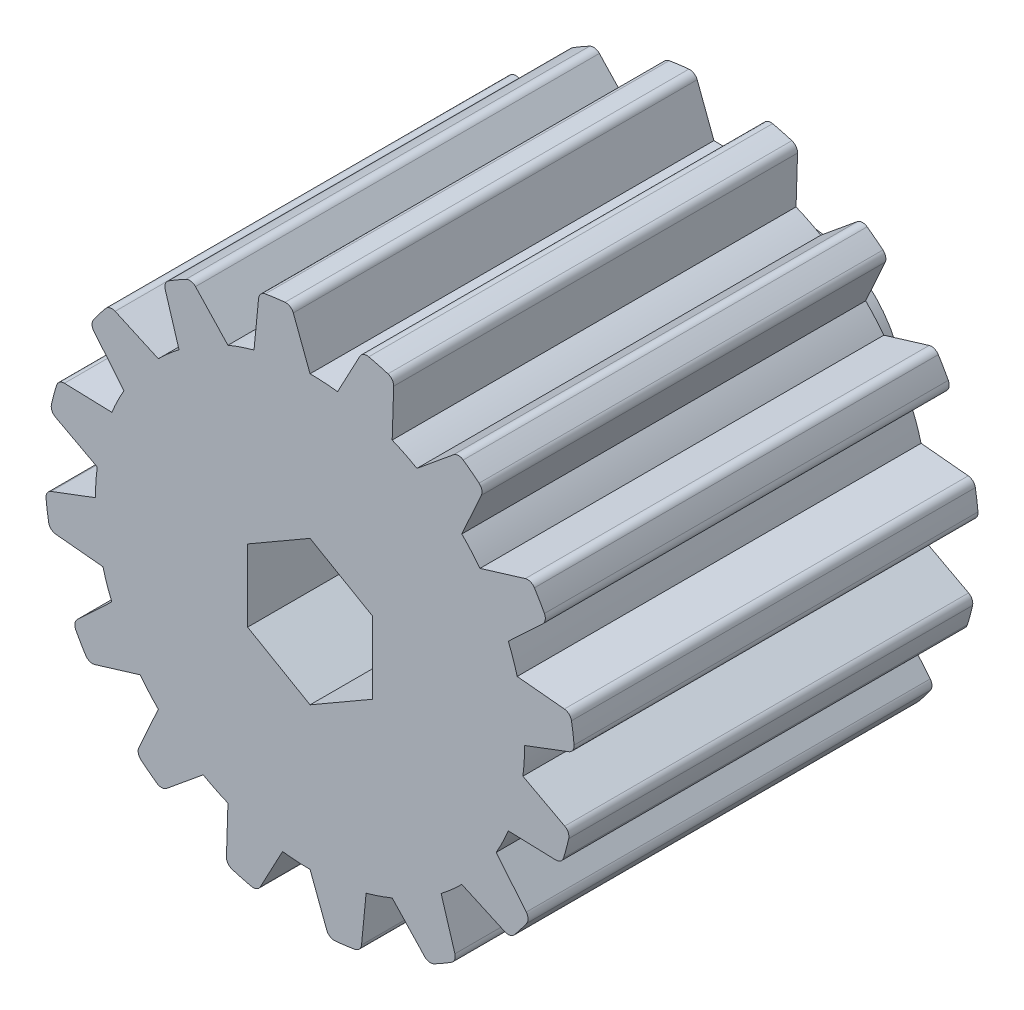
SolidWorks part; units mm, degrees
ref_plane "Alzado" through (0, 0, 0) normal (0, 0, 1) x (1, 0, 0)
ref_plane "Planta" through (0, 0, 0) normal (0, 1, 0) x (1, 0, 0)
ref_plane "Vista lateral" through (0, 0, 0) normal (1, 0, 0) x (0, 0, -1)
sketch "Croquis2" plane through (0, 0, 0) normal (0, 0, 1) x (1, 0, 0)
  line L0 (0, 0) -> (0, 7.9702) construction
  line L2 (-2.0817, 7.6936) -> (-1.9112, 9.4453)
  line L3 (-1.0408, 7.8319) -> (0, 0) construction
  line L4 (0, 7.9702) -> (-0.6221, 9.6166)
  line L5 (1.021, 7.9046) -> (1.8489, 9.4577)
  line L6 (3.0501, 7.3635) -> (3.1053, 9.1227)
  line L7 (3.9682, 6.9122) -> (5.3274, 8.0302)
  line L8 (5.6358, 5.6358) -> (6.3601, 7.2399)
  line L9 (6.3113, 4.8674) -> (7.9949, 5.3803)
  line L10 (7.3635, 3.0501) -> (8.6465, 4.2549)
  line L11 (7.6936, 2.0817) -> (9.4453, 1.9112)
  line L12 (7.9702, 0) -> (9.6166, 0.6221)
  line L13 (7.9046, -1.021) -> (9.4577, -1.8489)
  line L14 (7.3635, -3.0501) -> (9.1227, -3.1053)
  line L15 (6.9122, -3.9682) -> (8.0302, -5.3274)
  line L16 (5.6358, -5.6358) -> (7.2399, -6.3601)
  line L17 (4.8674, -6.3113) -> (5.3803, -7.9949)
  line L18 (3.0501, -7.3635) -> (4.2549, -8.6465)
  line L19 (2.0817, -7.6936) -> (1.9112, -9.4453)
  line L20 (0, -7.9702) -> (0.6221, -9.6166)
  line L21 (-1.021, -7.9046) -> (-1.8489, -9.4577)
  line L22 (-3.0501, -7.3635) -> (-3.1053, -9.1227)
  line L23 (-3.9682, -6.9122) -> (-5.3274, -8.0302)
  line L24 (-5.6358, -5.6358) -> (-6.3601, -7.2399)
  line L25 (-6.3113, -4.8674) -> (-7.9949, -5.3803)
  line L26 (-7.3635, -3.0501) -> (-8.6465, -4.2549)
  line L27 (-7.6936, -2.0817) -> (-9.4453, -1.9112)
  line L28 (-7.9702, 0) -> (-9.6166, -0.6221)
  line L29 (-7.9046, 1.021) -> (-9.4577, 1.8489)
  line L30 (-7.3635, 3.0501) -> (-9.1227, 3.1053)
  line L31 (-6.9122, 3.9682) -> (-8.0302, 5.3274)
  line L32 (-5.6358, 5.6358) -> (-7.2399, 6.3601)
  line L33 (-4.8674, 6.3113) -> (-5.3803, 7.9949)
  line L34 (-3.0501, 7.3635) -> (-4.2549, 8.6465)
  arc A0 (-4.8674, 6.3113) -> (-5.6358, 5.6358) centre (0, 0) ccw
  arc A1 (-7.5914, 6.2764) -> (-8.0413, 5.6886) centre (0, 0) ccw
  arc A2 (-1.6636, 9.7085) -> (-1.9112, 9.4453) centre (-1.6129, 9.4128) ccw
  arc A3 (-0.9298, 9.806) -> (-0.6221, 9.6166) centre (-0.9015, 9.5074) cw
  arc A4 (2.1783, 9.6061) -> (1.8489, 9.4577) centre (2.112, 9.3135) ccw
  arc A5 (2.8935, 9.4154) -> (3.1053, 9.1227) centre (2.8054, 9.1286) cw
  arc A6 (5.6886, 8.0413) -> (5.3274, 8.0302) centre (5.5153, 7.7964) ccw
  arc A7 (6.2764, 7.5914) -> (6.3601, 7.2399) centre (6.0852, 7.3602) cw
  arc A8 (8.3328, 5.2523) -> (7.9949, 5.3803) centre (8.0791, 5.0923) ccw
  arc A9 (8.7037, 4.6117) -> (8.6465, 4.2549) centre (8.4387, 4.4712) cw
  arc A10 (9.7085, 1.6636) -> (9.4453, 1.9112) centre (9.4128, 1.6129) ccw
  arc A11 (9.806, 0.9298) -> (9.6166, 0.6221) centre (9.5074, 0.9015) cw
  arc A12 (9.6061, -2.1783) -> (9.4577, -1.8489) centre (9.3135, -2.112) ccw
  arc A13 (9.4154, -2.8935) -> (9.1227, -3.1053) centre (9.1286, -2.8054) cw
  arc A14 (8.0413, -5.6886) -> (8.0302, -5.3274) centre (7.7964, -5.5153) ccw
  arc A15 (7.5914, -6.2764) -> (7.2399, -6.3601) centre (7.3602, -6.0852) cw
  arc A16 (5.2523, -8.3328) -> (5.3803, -7.9949) centre (5.0923, -8.0791) ccw
  arc A17 (4.6117, -8.7037) -> (4.2549, -8.6465) centre (4.4712, -8.4387) cw
  arc A18 (1.6636, -9.7085) -> (1.9112, -9.4453) centre (1.6129, -9.4128) ccw
  arc A19 (0.9298, -9.806) -> (0.6221, -9.6166) centre (0.9015, -9.5074) cw
  arc A20 (-2.1783, -9.6061) -> (-1.8489, -9.4577) centre (-2.112, -9.3135) ccw
  arc A21 (-2.8935, -9.4154) -> (-3.1053, -9.1227) centre (-2.8054, -9.1286) cw
  arc A22 (-5.6886, -8.0413) -> (-5.3274, -8.0302) centre (-5.5153, -7.7964) ccw
  arc A23 (-6.2764, -7.5914) -> (-6.3601, -7.2399) centre (-6.0852, -7.3602) cw
  arc A24 (-8.3328, -5.2523) -> (-7.9949, -5.3803) centre (-8.0791, -5.0923) ccw
  arc A25 (-8.7037, -4.6117) -> (-8.6465, -4.2549) centre (-8.4387, -4.4712) cw
  arc A26 (-9.7085, -1.6636) -> (-9.4453, -1.9112) centre (-9.4128, -1.6129) ccw
  arc A27 (-9.806, -0.9298) -> (-9.6166, -0.6221) centre (-9.5074, -0.9015) cw
  arc A28 (-9.6061, 2.1783) -> (-9.4577, 1.8489) centre (-9.3135, 2.112) ccw
  arc A29 (-9.4154, 2.8935) -> (-9.1227, 3.1053) centre (-9.1286, 2.8054) cw
  arc A30 (-8.0413, 5.6886) -> (-8.0302, 5.3274) centre (-7.7964, 5.5153) ccw
  arc A31 (-7.5914, 6.2764) -> (-7.2399, 6.3601) centre (-7.3602, 6.0852) cw
  arc A32 (-5.2523, 8.3328) -> (-5.3803, 7.9949) centre (-5.0923, 8.0791) ccw
  arc A33 (-4.6117, 8.7037) -> (-4.2549, 8.6465) centre (-4.4712, 8.4387) cw
  arc A34 (-4.6117, 8.7037) -> (-5.2523, 8.3328) centre (0, 0) ccw
  arc A35 (-0.9298, 9.806) -> (-1.6636, 9.7085) centre (0, 0) ccw
  arc A36 (2.8935, 9.4154) -> (2.1783, 9.6061) centre (0, 0) ccw
  arc A37 (6.2764, 7.5914) -> (5.6886, 8.0413) centre (0, 0) ccw
  arc A38 (8.7037, 4.6117) -> (8.3328, 5.2523) centre (0, 0) ccw
  arc A39 (9.4154, -2.8935) -> (9.6061, -2.1783) centre (0, 0) ccw
  arc A40 (7.5914, -6.2764) -> (8.0413, -5.6886) centre (0, 0) ccw
  arc A41 (-9.4154, 2.8935) -> (-9.6061, 2.1783) centre (0, 0) ccw
  arc A42 (-9.806, -0.9298) -> (-9.7085, -1.6636) centre (0, 0) ccw
  arc A43 (-8.7037, -4.6117) -> (-8.3328, -5.2523) centre (0, 0) ccw
  arc A44 (-6.2764, -7.5914) -> (-5.6886, -8.0413) centre (0, 0) ccw
  arc A45 (-2.8935, -9.4154) -> (-2.1783, -9.6061) centre (0, 0) ccw
  arc A46 (0.9298, -9.806) -> (1.6636, -9.7085) centre (0, 0) ccw
  arc A47 (4.6117, -8.7037) -> (5.2523, -8.3328) centre (0, 0) ccw
  arc A48 (-2.0817, 7.6936) -> (-3.0501, 7.3635) centre (0, 0) ccw
  arc A49 (1.021, 7.9046) -> (0, 7.9702) centre (0, 0) ccw
  arc A50 (3.9682, 6.9122) -> (3.0501, 7.3635) centre (0, 0) ccw
  arc A51 (6.3113, 4.8674) -> (5.6358, 5.6358) centre (0, 0) ccw
  arc A52 (7.6936, 2.0817) -> (7.3635, 3.0501) centre (0, 0) ccw
  arc A53 (7.9046, -1.021) -> (7.9702, 0) centre (0, 0) ccw
  arc A54 (9.806, 0.9298) -> (9.7085, 1.6636) centre (0, 0) ccw
  arc A55 (6.9122, -3.9682) -> (7.3635, -3.0501) centre (0, 0) ccw
  arc A56 (4.8674, -6.3113) -> (5.6358, -5.6358) centre (0, 0) ccw
  arc A57 (2.0817, -7.6936) -> (3.0501, -7.3635) centre (0, 0) ccw
  arc A58 (-1.021, -7.9046) -> (0, -7.9702) centre (0, 0) ccw
  arc A59 (-3.9682, -6.9122) -> (-3.0501, -7.3635) centre (0, 0) ccw
  arc A60 (-6.3113, -4.8674) -> (-5.6358, -5.6358) centre (0, 0) ccw
  arc A61 (-7.6936, -2.0817) -> (-7.3635, -3.0501) centre (0, 0) ccw
  arc A62 (-7.9046, 1.021) -> (-7.9702, 0) centre (0, 0) ccw
  arc A63 (-6.9122, 3.9682) -> (-7.3635, 3.0501) centre (0, 0) ccw
  dimension "D1" = 2.1
  dimension "D2" = 19.7
  dimension "D3" = 15.9404
  dimension "D6" = 0.6
  dimension "D4" = 1.76
extrude "Saliente-Extruir1" add sketch "Croquis2" along normal blind 15
sketch "Croquis5" plane through (0, 0, 0) normal (0, 0, -1) x (-1, 0, 0)
  circle A0 centre (0, 0) radius 4.5
  dimension "D1" = 9
extrude "Saliente-Extruir2" add sketch "Croquis5" along normal blind 6
scale "Escala1" scale about origin uniform scaling yes scale factor 1.5
sketch "Croquis7" plane through (0, 0, -9) normal (0, 0, -1) x (-1, 0, 0)
  circle A0 centre (0, 0) radius 10
  dimension "D1" = 20
extrude "Cortar-Extruir3" cut sketch "Croquis7" against normal blind 5.8 and the other way through all
sketch "Croquis8" plane through (0, 0, -3.2) normal (0, 0, -1) x (-1, 0, 0)
  circle A3 centre (0, 0) radius 5.5
  dimension "D1" = 11
extrude "Saliente-Extruir3" add sketch "Croquis8" along normal blind 1.87
sketch "Croquis10" plane through (0, 0, 22.5) normal (0, 0, 1) x (1, 0, 0)
  line L0 (0, 3.9) -> (0, -5.201) construction
  line L1 (0, 3.9) -> (-3.3775, 1.95) construction
  line L2 (-3.3775, 1.95) -> (-3.3775, -1.95) construction
  line L3 (-3.3775, -1.95) -> (0, -3.9) construction
  line L4 (0, -3.9) -> (3.3775, -1.95) construction
  line L5 (3.3775, -1.95) -> (3.3775, 1.95) construction
  line L6 (3.3775, 1.95) -> (0, 3.9) construction
  line L8 (0, 4.0155) -> (-3.4775, 2.0077)
  line L9 (-3.4775, 2.0077) -> (-3.4775, -2.0077)
  line L10 (-3.4775, -2.0077) -> (0, -4.0155)
  line L11 (0, -4.0155) -> (3.4775, -2.0077)
  line L12 (3.4775, -2.0077) -> (3.4775, 2.0077)
  line L13 (3.4775, 2.0077) -> (0, 4.0155)
  circle A0 centre (0, 0) radius 3.9 construction
  circle A1 centre (0, 0) radius 3.9 construction
  circle A3 centre (0, 0) radius 3.4775 construction
  dimension "D1" = 7.8
  dimension "D2" = 0.1
extrude "Cortar-Extruir4" cut sketch "Croquis10" against normal through all both and the other way through all
